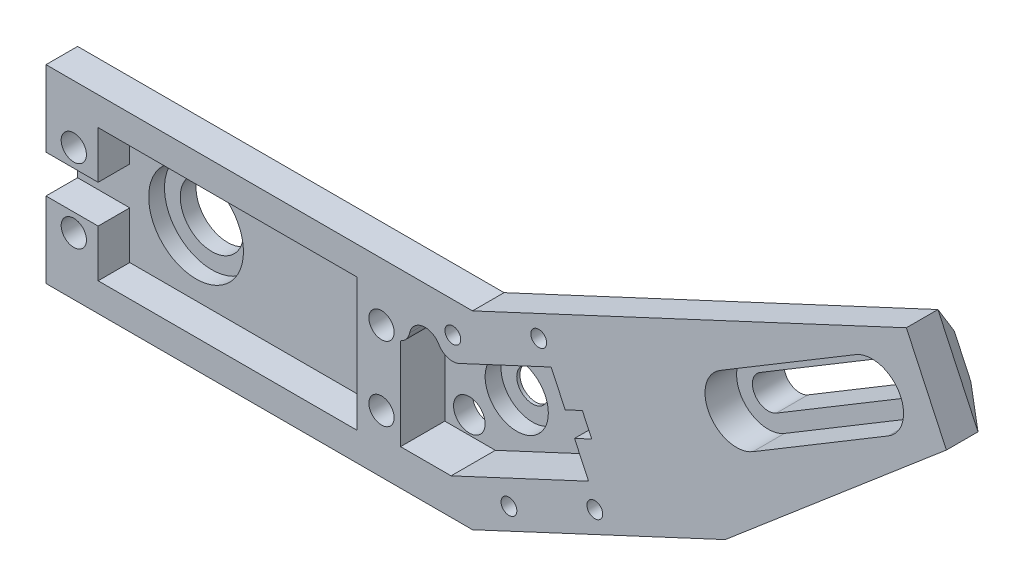
SolidWorks part; units mm, degrees
ref_plane "前视基准面" through (0, 0, 0) normal (0, 0, 1) x (1, 0, 0)
ref_plane "上视基准面" through (0, 0, 0) normal (0, 1, 0) x (1, 0, 0)
ref_plane "右视基准面" through (0, 0, 0) normal (1, 0, 0) x (0, 0, -1)
other "Configuration Table"
sketch "Sketch1" plane through (0, 0, 0) normal (0, 0, 1) x (1, 0, 0)
  line L1 (-28.75, -15) -> (28.75, -15)
  line L2 (-28.75, -15) -> (-28.75, 15)
  line L3 (-28.75, 15) -> (28.75, 15)
  line L4 (28.75, -15) -> (28.75, 15)
  line L5 (-28.75, -15) -> (28.75, 15) construction
  line L6 (-28.75, 15) -> (28.75, -15) construction
  point P0 (0, 0)
  dimension "D1" = 57.5
  dimension "D2" = 30
extrude "Boss-Extrude1" add sketch "Sketch1" along normal blind 30
sketch "Sketch2" plane through (0, 0, 30) normal (0, 0, 1) x (1, 0, 0)
  line L1 (-20.5, -10.5) -> (20.5, -10.5)
  line L2 (-20.5, -10.5) -> (-20.5, 10.5)
  line L3 (-20.5, 10.5) -> (20.5, 10.5)
  line L4 (20.5, -10.5) -> (20.5, 10.5)
  line L5 (-20.5, -10.5) -> (20.5, 10.5) construction
  line L6 (-20.5, 10.5) -> (20.5, -10.5) construction
  point P0 (0, 0)
  dimension "D1" = 41
  dimension "D2" = 21
extrude "Cut-Extrude1" cut sketch "Sketch2" against normal blind 25
ref_plane "Plane1" through (0, 0, 15) normal (0, 0, 1) x (1, 0, 0)
sketch "Sketch8" plane through (0, 0, 30) normal (0, 0, 1) x (1, 0, 0)
  line L0 (0, 0) -> (24.35, 0) construction
  line L1 (24.35, 0) -> (24.35, 6) construction
  line L2 (0, 0) -> (0, 15) construction
  line L3 (28.75, 15) -> (-28.75, 15) construction
  circle A0 centre (24.35, 6) radius 2
  circle A1 centre (24.35, -6) radius 2
  circle A2 centre (-24.35, -6) radius 2
  circle A3 centre (-24.35, 6) radius 2
  dimension "D3" = 4
  dimension "D1" = 6
  dimension "D2" = 24.35
extrude "Cut-Extrude6" cut sketch "Sketch8" against normal blind 10
sketch "Sketch10" plane through (0, 0, 5) normal (0, 0, 1) x (1, 0, 0)
  line L0 (0, 0) -> (-10, 0) construction
  circle A0 centre (-10, 0) radius 5
  dimension "D2" = 10
  dimension "D1" = 10
extrude "Cut-Extrude8" cut sketch "Sketch10" against normal blind 10
sketch "Sketch11" plane through (28.75, 0, 0) normal (1, 0, 0) x (0, 0, -1)
  line L0 (-30, 0) -> (0, 0) construction
  line L1 (-30, -15) -> (-30, 15) construction
  line L2 (0, 0) -> (-15, 0) construction
  line L3 (-15, -15) -> (-15, 15)
  line L4 (-30, 15) -> (0, 15) construction
  line L5 (-15, 15) -> (-11.75, 15)
  line L6 (-11.75, 15) -> (-11.75, 22.5)
  line L7 (-11.75, 22.5) -> (-18.25, 22.5)
  line L8 (-18.25, 22.5) -> (-18.25, 15)
  line L9 (-18.25, 15) -> (-15, 15)
  line L10 (7.5, 3.25) -> (0, 3.25)
  line L11 (0, 3.25) -> (0, 0)
  line L12 (0, -3.25) -> (7.5, -3.25)
  line L13 (0, 0) -> (0, -3.25)
  line L14 (7.5, -3.25) -> (7.5, 3.25)
  line L15 (-11.75, -22.5) -> (-11.75, -15)
  line L16 (-11.75, -15) -> (-15, -15)
  line L17 (-18.25, -15) -> (-18.25, -22.5)
  line L18 (-15, -15) -> (-18.25, -15)
  line L19 (-18.25, -22.5) -> (-11.75, -22.5)
  line L20 (-37.5, -3.25) -> (-30, -3.25)
  line L21 (-30, -3.25) -> (-30, 0)
  line L22 (-30, 3.25) -> (-37.5, 3.25)
  line L23 (-30, 0) -> (-30, 3.25)
  line L24 (-37.5, 3.25) -> (-37.5, -3.25)
  circle A0 centre (-15, 0) radius 7.5 construction
  point P12 (-15, 0)
  point P34 (-15, 0)
  line M5 (0, -15) -> (0, 15)
  line M6 (0, 15) -> (-30, 15)
  line M7 (-30, 15) -> (-30, -15)
  line M8 (-30, -15) -> (0, -15)
  dimension "D1" = 15
  dimension "D2" = 6.5
  dimension "D3" = 7.5
  dimension "D4" = 4
extrude "Boss-Extrude2" [suppressed] add sketch "Sketch11" against normal up to surface (8.25 mm away) contours L22 L24 L20 M7 | L17 L19 L15 M8 | L12 L14 L10 M5 | L7 L8 L6 M6
sketch "Sketch12" plane through (28.75, 0, 0) normal (1, 0, 0) x (0, 0, -1)
  line L20 (-36.5, 15) -> (-30, 15)
  line L21 (-30, -15) -> (-30, -21.5)
  line L22 (0, -15) -> (-11.75, -15)
  line L23 (0, 3.25) -> (0, 15)
  line L40 (0, -15) -> (0, 15)
  line L45 (0, 15) -> (-30, 15)
  line L50 (-30, 15) -> (-30, -15)
  line L55 (-30, -15) -> (0, -15)
  line L60 (0, -15) -> (0, 15)
  line L65 (0, 15) -> (-30, 15)
  line L70 (-30, 15) -> (-30, -15)
  line L75 (-30, -15) -> (0, -15)
  dimension "D1" = 0
extrude "Boss-Extrude3" [suppressed] add sketch "Sketch12" along normal blind 30
sketch "Sketch13" plane through (0, 0, 30) normal (0, 0, 1) x (1, 0, 0)
  line L0 (28.75, 15) -> (38.75, 15)
  line L1 (38.75, 15) -> (107.4107, 47.017)
  line L3 (113.75, 33.4224) -> (78.75, 3.6523)
  line L4 (78.75, 3.6523) -> (38.75, -15)
  line L5 (38.75, -15) -> (28.75, -15)
  line L6 (-28.75, -15) -> (28.75, -15) construction
  line L7 (38.75, 15) -> (38.75, -15) construction
  line L8 (38.75, -15) -> (93.0307, -15) construction
  line L9 (78.75, 3.6523) -> (97.9021, 3.6523) construction
  line L10 (38.75, 15) -> (83.4484, 15) construction
  line L11 (28.75, -15) -> (28.75, 15)
  line L12 (107.4107, 47.017) -> (113.75, 33.4224)
  dimension "D1" = 10
  dimension "D2" = 25
  dimension "D3" = 40
  dimension "D4" = 25
  dimension "D5" = 15
  dimension "D6" = 75
extrude "Boss-Extrude4" add sketch "Sketch13" against normal blind 30
sketch "Sketch16" plane through (1.1757, -2.5212, 0) normal (-0.4226, 0.9063, 0) x (0.9063, 0.4226, 0)
  line L0 (117.2174, -15) -> (97.2174, -15) construction
  line L1 (117.2174, 0) -> (117.2174, -30) construction
  line L2 (-16.5, -15) -> (16.5, -15) construction
  line L3 (97.2174, -15) -> (74.7174, -15) construction
  line L4 (67.2174, -15) -> (82.2174, -15) construction
  line L5 (67.2174, -12.5) -> (82.2174, -12.5)
  line L6 (67.2174, -17.5) -> (82.2174, -17.5)
  circle A0 centre (97.2174, -15) radius 5
  arc A1 (67.2174, -12.5) -> (67.2174, -17.5) centre (67.2174, -15) ccw
  arc A2 (82.2174, -17.5) -> (82.2174, -12.5) centre (82.2174, -15) ccw
  point P10 (74.7174, -15)
  dimension "D1" = 10
  dimension "D4" = 2.5
  dimension "D2" = 20
  dimension "D3" = 15
  dimension "D5" = 22.5
extrude "Cut-Extrude10" cut sketch "Sketch16" against normal blind 30
chamfer "Chamfer5" distance 5 angle 45 13 edges at (-28.75, 0, 0) (5, -15, 0) (58.75, -5.6738, 0) (96.25, 18.5374, 0) (110.5804, 40.2197, 0) (73.0804, 31.0085, 0) (5, 15, 0) (5, -15, 30) (58.75, -5.6738, 30) (96.25, 18.5374, 30) (73.0804, 31.0085, 30) (5, 15, 30) (110.5804, 40.2197, 30)
sketch "Sketch20" plane through (0, 0, 5) normal (0, 0, 1) x (1, 0, 0)
  circle A0 centre (-10, 0) radius 7.5
  dimension "D1" = 15
extrude "Cut-Extrude13" cut sketch "Sketch20" against normal blind 2.5
sketch "Sketch30" plane through (0, 15, 0) normal (0, 1, 0) x (1, 0, 0)
  line L0 (-28.75, -30) -> (-28.75, -10)
  line L1 (-28.75, -25) -> (-28.75, -5) construction
  line L2 (-28.75, -10) -> (113.75, -10)
  line L3 (113.75, -5) -> (113.75, -25) construction
  line L4 (113.75, -10) -> (113.75, -30)
  line L5 (113.75, -30) -> (-28.75, -30)
  dimension "D1" = 20
extrude "Cut-Extrude16" cut sketch "Sketch30" against normal through all both and the other way through all
sketch "Sketch31" plane through (0, 0, 10) normal (0, 0, 1) x (1, 0, 0)
  line L2 (38.75, -15) -> (38.75, 0) construction
  line L3 (38.75, 0) -> (43.2815, 2.1131) construction
  line L4 (38.75, -15) -> (78.75, 3.6523) construction
  line L5 (30.4265, -5.8122) -> (57.6157, 6.8663)
  line L6 (35.3642, -9.3025) -> (57.1156, 0.8404)
  line L7 (35.3642, -9.3025) -> (29.4475, 3.3858)
  line L8 (29.4475, 3.3858) -> (51.1989, 13.5287)
  line L9 (57.1156, 0.8404) -> (51.1989, 13.5287)
  line L10 (35.3642, -9.3025) -> (51.1989, 13.5287) construction
  line L11 (29.4475, 3.3858) -> (57.1156, 0.8404) construction
  line L12 (30.4265, -5.8122) -> (28.9473, -2.6401)
  line L13 (57.6157, 6.8663) -> (56.1366, 10.0384)
  line L14 (28.9473, -2.6401) -> (56.1366, 10.0384)
  line L15 (30.4265, -5.8122) -> (56.1366, 10.0384) construction
  line L16 (57.6157, 6.8663) -> (28.9473, -2.6401) construction
  line L17 (43.2815, 2.1131) -> (56.8762, 8.4524) construction
  dimension "D1" = 24
  dimension "D2" = 14
  dimension "D3" = 5
  dimension "D4" = 90
  dimension "D5" = 30
  dimension "D6" = 3.5
  dimension "D7" = 15
extrude "Cut-Extrude17" cut sketch "Sketch31" against normal blind 7 contours L7 L14 L9 L8 | L6 L9 L5 L7 | L14 L12 L5 L7 | L14 L7 L5 L9 | L14 L9 L5 L13 region at (31.0464, -3.5923, 10) region at (43.2815, 2.1131, 10) region at (45.1305, -1.852, 10) region at (55.5167, 7.8184, 10) region at (41.4326, 6.0782, 10)
sketch "Sketch33" plane through (0, 0, 0) normal (0, 0, 1) x (1, 0, 0)
  line L0 (110.5804, 40.2197) -> (125.3057, 40.2197) construction
  line L1 (113.75, 33.4224) -> (107.4107, 47.017) construction
  line L4 (110.5804, 40.2197) -> (101.9744, 35.0487) construction
  line L6 (80.5452, 22.1728) -> (101.9744, 35.0487) construction
  line L7 (79.2576, 24.3157) -> (100.6868, 37.1916)
  line L8 (81.8328, 20.0299) -> (103.262, 32.9058)
  arc A1 (79.2576, 24.3157) -> (81.8328, 20.0299) centre (80.5452, 22.1728) ccw
  arc A2 (103.262, 32.9058) -> (100.6868, 37.1916) centre (101.9744, 35.0487) ccw
  point P4 (91.2598, 28.6108)
  dimension "D1" = 2.5
  dimension "D2" = 25
  dimension "D3" = 10.04
  dimension "D4" = 149
extrude "Cut-Extrude19" cut sketch "Sketch33" along normal through all contours L8 A2 L7 A1 region at (91.2598, 28.6108, 0)
sketch "Sketch34" plane through (0, 0, 0) normal (0, 0, -1) x (-1, 0, 0)
  line L0 (-101.9744, 35.0487) -> (-80.5452, 22.1728) construction
  line L1 (-99.3992, 39.3346) -> (-77.97, 26.4586)
  line L2 (-104.5496, 30.7629) -> (-83.1204, 17.8869)
  arc A0 (-99.3992, 39.3346) -> (-104.5496, 30.7629) centre (-101.9744, 35.0487) ccw
  arc A1 (-83.1204, 17.8869) -> (-77.97, 26.4586) centre (-80.5452, 22.1728) ccw
  point P4 (-91.2598, 28.6108)
  dimension "D1" = 5
extrude "Cut-Extrude20" [suppressed] cut sketch "Sketch34" against normal blind 5
sketch "Sketch35" plane through (0, 0, 0) normal (0, 0, -1) x (-1, 0, 0)
  line L0 (-38.75, -15) -> (-38.75, 15) construction
  line L1 (-38.75, 15) -> (-38.75, 0) construction
  line L2 (-38.75, 0) -> (-31.25, 0) construction
  line L3 (-31.25, 0) -> (-31.25, -6.5) construction
  circle A0 centre (-38.75, 0) radius 2.5
  circle A1 centre (-31.25, -6.5) radius 2.5
  circle A2 centre (-31.25, 6.5) radius 2.5
  dimension "D1" = 5
  dimension "D2" = 5
  dimension "D3" = 7.5
  dimension "D4" = 6.5
extrude "Cut-Extrude21" cut sketch "Sketch35" against normal through all
sketch "Sketch37" plane through (0, 0, 10) normal (0, 0, 1) x (1, 0, 0)
  line L0 (-28.75, 0) -> (-20.5, 0) construction
  line L1 (-28.75, -15) -> (-28.75, 15) construction
  line L2 (-20.5, 10.5) -> (-20.5, -10.5) construction
  line L3 (-20.5, 10.5) -> (-20.5, -10.5) construction
  line L4 (-28.75, -3) -> (-20.5, -3)
  line L5 (-28.75, -3) -> (-28.75, 3)
  line L6 (-28.75, 3) -> (-20.5, 3)
  line L7 (-20.5, -3) -> (-20.5, 3)
  line L8 (-28.75, -3) -> (-20.5, 3) construction
  line L9 (-28.75, 3) -> (-20.5, -3) construction
  point P6 (-24.625, 0)
  dimension "D1" = 6
extrude "Cut-Extrude23" cut sketch "Sketch37" against normal blind 5
sketch "Sketch38" plane through (0, 0, 10) normal (0, 0, 1) x (1, 0, 0)
  line L0 (80.5452, 22.1728) -> (101.9744, 35.0487) construction
  line L1 (77.97, 26.4586) -> (99.3992, 39.3346)
  line L2 (83.1204, 17.8869) -> (104.5496, 30.7629)
  arc A0 (77.97, 26.4586) -> (83.1204, 17.8869) centre (80.5452, 22.1728) ccw
  arc A1 (104.5496, 30.7629) -> (99.3992, 39.3346) centre (101.9744, 35.0487) ccw
  point P4 (91.2598, 28.6108)
  dimension "D1" = 5
extrude "Cut-Extrude24" cut sketch "Sketch38" against normal blind 5
sketch "Sketch40" plane through (0, 0, 3) normal (0, 0, 1) x (1, 0, 0)
  circle A0 centre (38.75, 0) radius 5
  dimension "D1" = 10
extrude "Cut-Extrude25" cut sketch "Sketch40" against normal blind 2.5
sketch "Sketch41" plane through (0, 0, 10) normal (0, 0, 1) x (1, 0, 0)
  line L0 (0, 10.5) -> (0, -10.5) construction
  line L1 (-24.35, 0) -> (-24.35, 5.85) construction
  line L2 (20.5, 10.5) -> (-20.5, 10.5) construction
  line L3 (-20.5, -10.5) -> (20.5, -10.5) construction
  line L4 (0, -10.5) -> (0, 0) construction
  line L5 (0, 0) -> (-24.35, 0) construction
  circle A0 centre (-24.35, 5.85) radius 2
  circle A1 centre (-24.35, -5.85) radius 2
  circle A4 centre (24.35, -5.85) radius 2
  circle A5 centre (24.35, 5.85) radius 2
  dimension "D1" = 4
  dimension "D2" = 5.85
  dimension "D3" = 24.35
extrude "Cut-Extrude26" cut sketch "Sketch41" against normal blind 10
sketch "Sketch44" plane through (0, 0, 10) normal (0, 0, 1) x (1, 0, 0)
  line L0 (27.3642, -9.3025) -> (35.3642, -9.3025)
  line L2 (33.3642, 5.2122) -> (35.3642, -9.3025)
  line L4 (33.3642, 5.2122) -> (27.3642, 5.2122)
  line L5 (27.3642, 5.2122) -> (27.3642, -9.3025)
  line L6 (27.3642, -9.3025) -> (35.3642, -9.3025)
  line L7 (33.4038, 5.2307) -> (51.1989, 13.5287) construction
  line L8 (33.4038, 5.2307) -> (51.1989, 13.5287) construction
  line M28 (33.1454, -4.5444) -> (32.9272, -4.6461)
  arc M29 (32.9272, -4.6461) -> (29.7982, -4.4648) centre (31.25, -6.5) cw
  line M31 (29.7982, -4.4648) -> (28.9473, -2.6401)
  line M32 (28.9473, -2.6401) -> (31.6663, -1.3723)
  line M33 (31.6663, -1.3723) -> (29.4475, 3.3858)
  line M43 (35.3642, -9.3025) -> (33.1454, -4.5444)
  dimension "D1" = 90
  dimension "D2" = 8
  dimension "D3" = 6
extrude "Cut-Extrude27" cut sketch "Sketch44" against normal up to surface (7 mm away) contours L4 L5 L0 M43 M28 M29 M31 M32 M33 region at (30.888, -2.3907, 10) up to face at (43.75, 0, 3)
fillet "Fillet3" radius 2.5 1 edges at (33.4038, 5.2307, 6.5)
fillet "Fillet4" radius 2.5 1 edges at (29.1072, 5.2122, 6.5)
sketch "Sketch45" plane through (0, 0, 10) normal (0, 0, 1) x (1, 0, 0)
  line L0 (43.9169, 10.133) -> (42.4377, 13.3051) construction
  line L1 (36.6349, 6.7373) -> (51.1989, 13.5287) construction
  line L2 (42.4377, 13.3051) -> (49.235, 16.4747) construction
  line L3 (56.8762, 8.4524) -> (38.75, 0) construction
  line L4 (57.6157, 6.8663) -> (56.1366, 10.0384) construction
  circle A0 centre (49.235, 16.4747) radius 1.25
  circle A1 centre (35.6404, 10.1354) radius 1.25
  circle A2 centre (58.11, -2.5577) radius 1.25
  circle A3 centre (44.5154, -8.897) radius 1.25
  dimension "D1" = 2.5
  dimension "7.5" = 7.5
  dimension "D3" = 3.5
extrude "Cut-Extrude28" cut sketch "Sketch45" against normal through all
